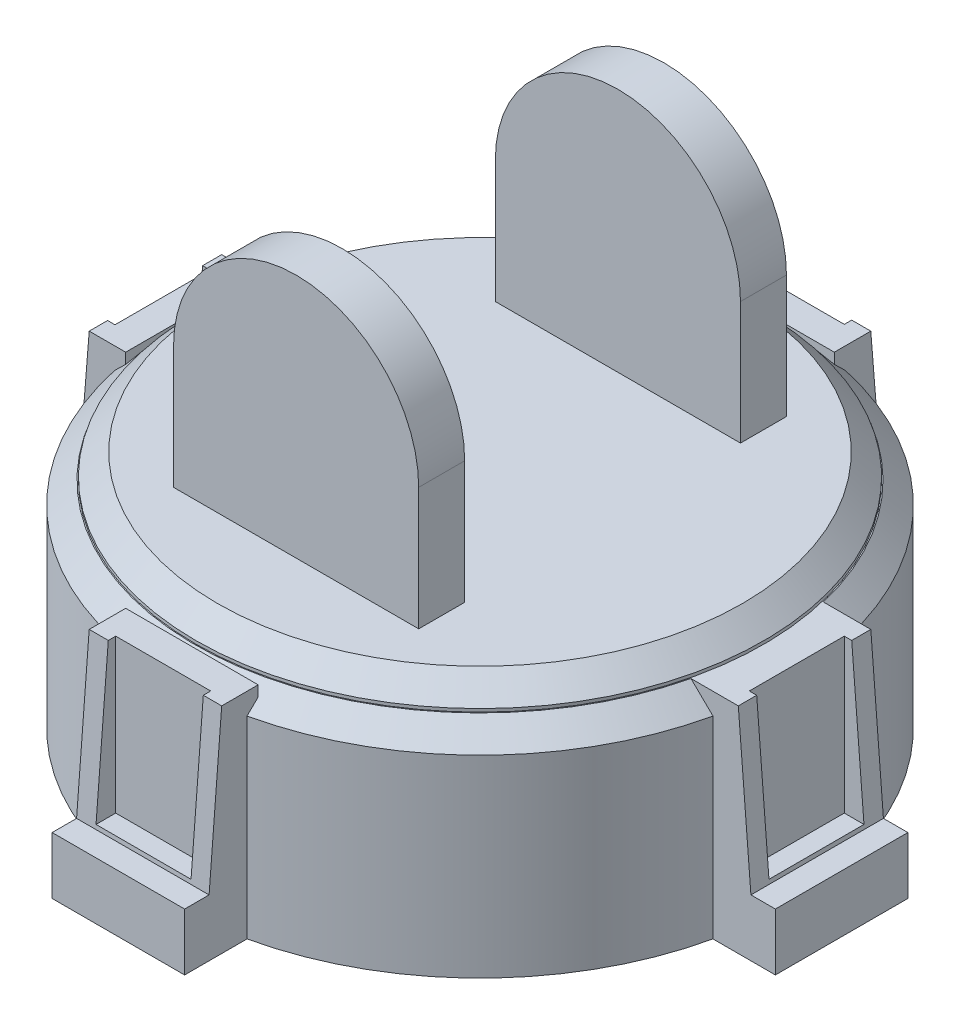
SolidWorks part; units mm, degrees
ref_plane "Front Plane" through (0, 0, 0) normal (0, 0, 1) x (1, 0, 0)
ref_plane "Top Plane" through (0, 0, 0) normal (0, 1, 0) x (1, 0, 0)
ref_plane "Right Plane" through (0, 0, 0) normal (1, 0, 0) x (0, 0, -1)
sketch "Sketch1" plane through (0, 0, 0) normal (0, 1, 0) x (1, 0, 0)
  circle A0 centre (0, 0) radius 50
  dimension "D1" = 100
extrude "Boss-Extrude1" add sketch "Sketch1" along normal blind 35
sketch "Sketch2" plane through (0, 35, 0) normal (0, 1, 0) x (1, 0, 0)
  circle A0 centre (0, 0) radius 46.3369
extrude "Boss-Extrude2" add sketch "Sketch2" along normal blind 4
chamfer "Chamfer5" distance 3.5 angle 45 1 edges at (0, 39, 46.3369)
sketch "Sketch3" plane through (0, 35, 0) normal (0, 1, 0) x (1, 0, 0)
  line L0 (0, 0) -> (83.3952, 0) construction
  line L1 (47, -10.8079) -> (47, 10.8079)
  line L2 (47, 10.8079) -> (59, 10.8079)
  line L3 (59, 10.8079) -> (59, -10.8079)
  line L4 (47, -10.8079) -> (59, -10.8079)
  point P8 (59, 0)
  point P9 (47, 0)
  dimension "D1" = 47
  dimension "D2" = 12
extrude "Boss-Extrude3" add sketch "Sketch3" against normal blind 35
sketch "Sketch4" plane through (0, 35, 0) normal (0, 1, 0) x (1, 0, 0)
  line L0 (0, 0) -> (73.7281, 0) construction
  line L1 (51.7449, 7.8079) -> (59, 7.8079)
  line L2 (59, -10.8079) -> (59, 10.8079) construction
  line L3 (59, 7.8079) -> (59, -7.6921)
  line L4 (59, -7.6921) -> (51.7449, -7.6921)
  line L5 (51.7449, -7.6921) -> (51.7449, 7.8079)
  line L6 (59, 10.8079) -> (48.8179, 10.8079) construction
  line L7 (48.8179, -10.8079) -> (59, -10.8079) construction
  arc A0 (48.8179, 10.8079) -> (48.8179, -10.8079) centre (0, 0) ccw construction
  arc A1 (48.8179, 10.8079) -> (48.8179, -10.8079) centre (0, 0) ccw
  dimension "D1" = 15.5
  dimension "D2" = 3
  dimension "D3" = 7.2551
  dimension "D4" = 3.1158
  dimension "D5" = 15.5
extrude "Cut-Extrude1" cut sketch "Sketch4" against normal blind 25 contours L5 L1 L3 L4
ref_plane "Plane1" through (48.8179, 35, 10.8079) normal (1, 0, 0) x (0, 0, -1)
sketch "Sketch7" plane through (0, 0, 10.8079) normal (0, 0, 1) x (1, 0, 0)
  line L0 (52.9521, 35) -> (55.0101, 9.3196)
  line L1 (48.8179, 35) -> (59, 35) construction
  line L2 (55.0101, 9.3196) -> (59, 9.3196)
  line L3 (59, 0) -> (59, 35) construction
  line L4 (59, 9.3196) -> (59, 35)
  line L5 (59, 35) -> (52.9521, 35)
extrude "Cut-Extrude2" cut sketch "Sketch7" against normal blind 23 contours L5 L0 L2 L4
chamfer "Chamfer6" distance 3.5 angle 45 1 edges at (-50, 35, 0)
mirror "Mirror1" about plane through (0, 0, 0) normal (1, 0, 0) of "Boss-Extrude3", "Cut-Extrude1", "Cut-Extrude2"
sketch "Sketch8" plane through (0, 39, 0) normal (0, 1, 0) x (1, 0, 0)
  circle A0 centre (0, 0) radius 6.5132
pattern_circular "CirPattern2" count 4 over 360 about axis through (0, 35, 0) along (0, -1, 0) of "Mirror1"
sketch "Sketch9" plane through (0, 0, 0) normal (0, 0, 1) x (1, 0, 0)
  line L0 (42.8369, 39) -> (-42.8369, 39) construction
  line L1 (-20, 59) -> (20, 59)
  line L2 (-20, 59) -> (-20, 39)
  line L3 (-20, 39) -> (20, 39)
  line L4 (20, 59) -> (20, 39)
  line L5 (-20, 59) -> (20, 39) construction
  line L6 (-20, 39) -> (20, 59) construction
  point P0 (0, 49)
  point P7 (0, 11.6502)
  dimension "D1" = 20
  dimension "D2" = 40
  dimension "D3" = 0
  dimension "D4" = 0
extrude "Boss-Extrude5" add sketch "Sketch9" along normal blind 30
sketch "Sketch10" plane through (0, 0, 30) normal (0, 0, 1) x (1, 0, 0)
  line L0 (20, 59) -> (-20, 59) construction
  circle A0 centre (0, 59) radius 20
extrude "Boss-Extrude6" add sketch "Sketch10" against normal blind 30
sketch "Sketch12" plane through (0, 39, 0) normal (0, 1, 0) x (1, 0, 0)
  line L0 (20, -30) -> (20, 0) construction
  line L1 (-20, 22.5) -> (20, 22.5)
  line L2 (-20, 22.5) -> (-20, -22.5)
  line L3 (-20, -22.5) -> (20, -22.5)
  line L4 (20, 22.5) -> (20, -22.5)
  line L5 (-20, 22.5) -> (20, -22.5) construction
  line L6 (-20, -22.5) -> (20, 22.5) construction
  point P0 (0, 0)
  dimension "D1" = 45
extrude "Cut-Extrude4" cut sketch "Sketch12" along normal blind 86
mirror "Mirror4" about plane through (0, 0, 0) normal (0, 0, 1) of "Boss-Extrude6", "Boss-Extrude5", "Cut-Extrude4"
